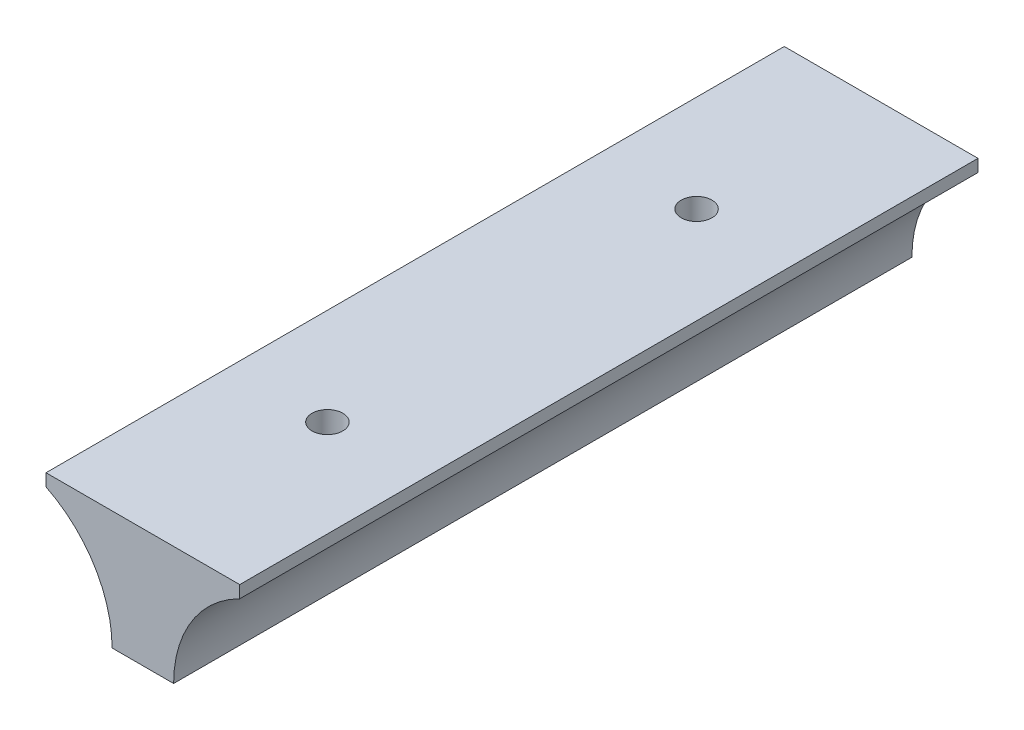
SolidWorks part; units mm, degrees
ref_plane "Front" through (0, 0, 0) normal (0, 0, 1) x (1, 0, 0)
ref_plane "Top" through (0, 0, 0) normal (0, 1, 0) x (1, 0, 0)
ref_plane "Right" through (0, 0, 0) normal (1, 0, 0) x (0, 0, -1)
sketch "Sketch1" plane through (0, 0, 0) normal (0, 0, 1) x (1, 0, 0)
  line L0 (-2.5, 0) -> (2.5, 0)
  line L1 (7.8722, 8.65) -> (7.8722, 9.65)
  line L2 (7.8722, 9.65) -> (-7.8722, 9.65)
  line L3 (-7.8722, 9.65) -> (-7.8722, 8.65)
  arc A0 (2.5, 0) -> (7.8722, 8.65) centre (12.15, 0) cw
  arc A1 (-2.5, 0) -> (-7.8722, 8.65) centre (-12.15, 0) ccw
  point P9 (0, 0)
  point P10 (0, 9.65)
  dimension "D1" = 9.65
  dimension "D2" = 9.65
  dimension "D3" = 5
  dimension "D4" = 1
extrude "Boss-Extrude1" add sketch "Sketch1" along normal blind 60
sketch "Sketch2" plane through (0, 9.65, 0) normal (0, 1, 0) x (1, 0, 0)
  line L0 (0, -60) -> (0, 0) construction
  line L1 (7.8722, -60) -> (-7.8722, -60) construction
  line L2 (7.8722, 0) -> (-7.8722, 0) construction
  point P6 (0, -45)
  point P7 (0, -15)
  dimension "D1" = 15
  dimension "D2" = 15
hole_wizard "Ø2.5mm Dowel Hole1" positions "3DSketch1" profile "Sketch3" hole size "Ø2.5" standard "ANSI Metric" end condition up to next
sketch3d "3DSketch1"
  point P0 (0, 9.65, 45)
  point P3 (0, 9.65, 15)
sketch "Sketch3" plane through (0, 9.65, 45) normal (1, 0, 0) x (0, 0, 1)
  line L0 (0, 0) -> (0, 9.65)
  line L1 (0, 9.65) -> (1.25, 9.65)
  line L2 (1.25, 9.65) -> (1.25, 0)
  line L5 (1.25, 0) -> (0, 0)
  line L11 (0, -6.35) -> (0, 107.95) construction
  dimension "Thru Hole Dia." = 2.5
  dimension "Thru Hole Depth" = 9.65
